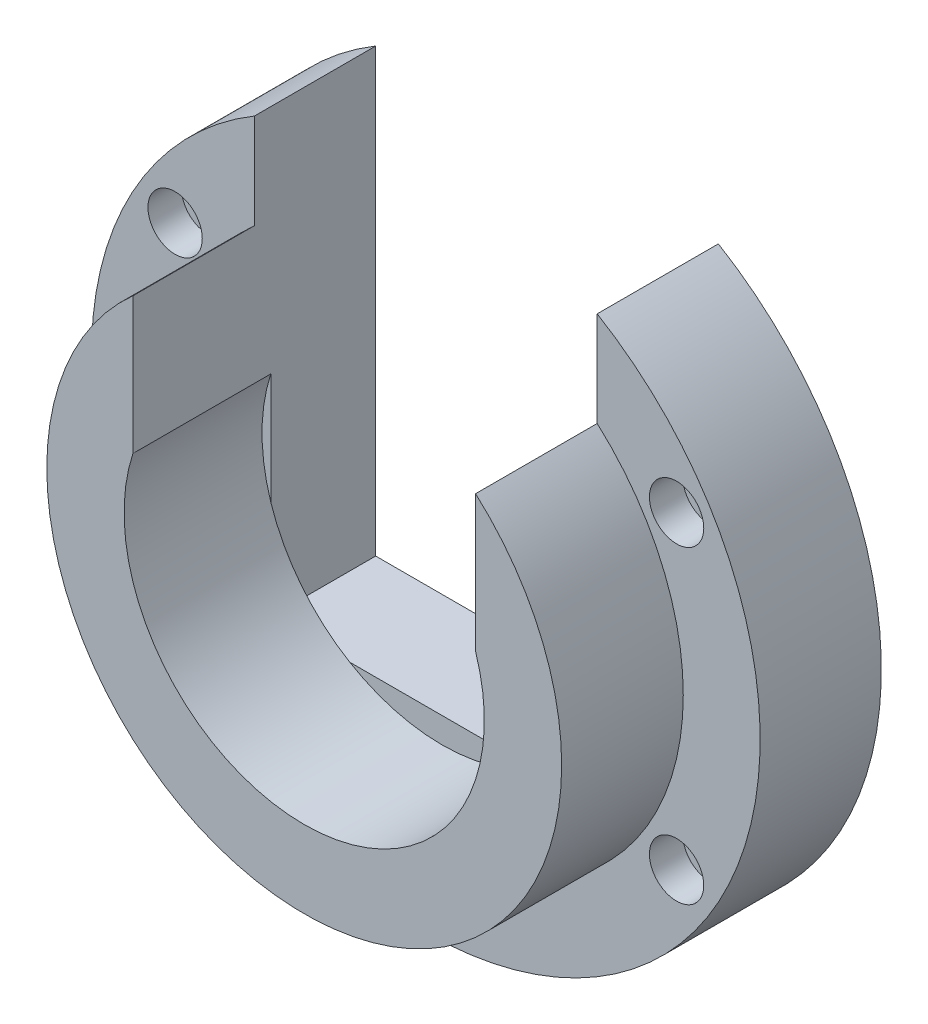
SolidWorks part; units mm, degrees
ref_plane "Front Plane" through (0, 0, 0) normal (0, 0, 1) x (1, 0, 0)
ref_plane "Top Plane" through (0, 0, 0) normal (0, 1, 0) x (1, 0, 0)
ref_plane "Right Plane" through (0, 0, 0) normal (1, 0, 0) x (0, 0, -1)
sketch "Sketch2" plane through (0, 0, 0) normal (0, 0, 1) x (1, 0, 0)
  line L0 (-20.5, 34.3475) -> (-20.5, -18.5)
  line L1 (-20.5, -18.5) -> (20.5, -18.5)
  line L2 (20.5, -18.5) -> (20.5, 34.3475)
  circle A0 centre (0, 0) radius 40
  point P7 (28.3381, 28.2304)
  point P8 (-27.2485, 29.2835)
  dimension "D1" = 80
  dimension "D2" = 18.5
  dimension "D3" = 20.5
extrude "Boss-Extrude1" add sketch "Sketch2" along normal blind 14.5 contours L0 A0 L2 L1 region at (-21.5921, 7.9237, 0)
sketch "Sketch1" plane through (0, 0, 14.5) normal (0, 0, 1) x (1, 0, 0)
  line L0 (20.5, -18.5) -> (20.5, 34.3475) construction
  line L1 (-20.5, 34.3475) -> (-20.5, -18.5) construction
  line L2 (20.5, -18.5) -> (20.5, 34.3475)
  line L3 (-20.5, 34.3475) -> (-20.5, -18.5)
  circle A0 centre (0, 0) radius 21.55
  circle A1 centre (0, 0) radius 30.8
  point P3 (0, 0)
  line M3 (-20.5, -18.5) -> (-20.5, 34.3475)
  line M5 (20.5, 34.3475) -> (20.5, -18.5)
  line M6 (20.5, -18.5) -> (-20.5, -18.5)
  dimension "D1" = 43.1
  dimension "D2" = 61.6
extrude "Cut-Extrude1" cut sketch "Sketch1" against normal offset from surface (1.95 mm away) 12.55 contours A0 up to face at (0, -10.6631, 0)
extrude "Boss-Extrude3" add sketch "Sketch1<3>" along normal blind 16.5 from surface contours A1 L2 A0 M3 M5 M6 | A0 M3 M6 | A0 M6 M5 region at (17.7319, -15.0925, 14.5) region at (21.3178, -12.5724, 14.5) region at (-17.7319, -15.0925, 14.5) starting at face at (0, -20.025, 12.55)
sketch "Sketch1<3>" plane through (0, 0, 14.5) normal (0, 0, 1) x (1, 0, 0) same geometry as "Sketch1"
sketch "Sketch4" plane through (0, 0, 14.5) normal (0, 0, 1) x (1, 0, 0)
  circle A0 centre (30, 18.5084) radius 1.7
  circle A1 centre (30, -18.5084) radius 1.7
  circle A2 centre (-30, 18.5084) radius 1.7
  circle A3 centre (-30, -18.5084) radius 1.7
  circle A4 centre (0, 0) radius 35.25 construction
  point P14 (33.6067, 10.6134)
  point P15 (30.8292, -17.0766)
  point P16 (-27.9841, -21.423)
  point P17 (-31.6375, 16.1597)
  point P18 (-31.439, 15.9261)
  point P19 (0, 0)
  point P20 (0, 0)
  point P21 (0, 0)
  point P22 (32.2395, 14.2361)
  dimension "D1" = 3.4
  dimension "D3" = 70.5
  dimension "D2" = 30
extrude "Cut-Extrude2" cut sketch "Sketch4" against normal through all
sketch "Sketch5" plane through (0, 0, 14.5) normal (0, 0, 1) x (1, 0, 0)
  circle A0 centre (-30, 18.5084) radius 3.25
  circle A1 centre (30, 18.5084) radius 3.25
  circle A2 centre (30, -18.5084) radius 3.25
  circle A3 centre (-30, -18.5084) radius 3.25
  dimension "D1" = 6.5
extrude "Cut-Extrude3" cut sketch "Sketch5" against normal blind 4
